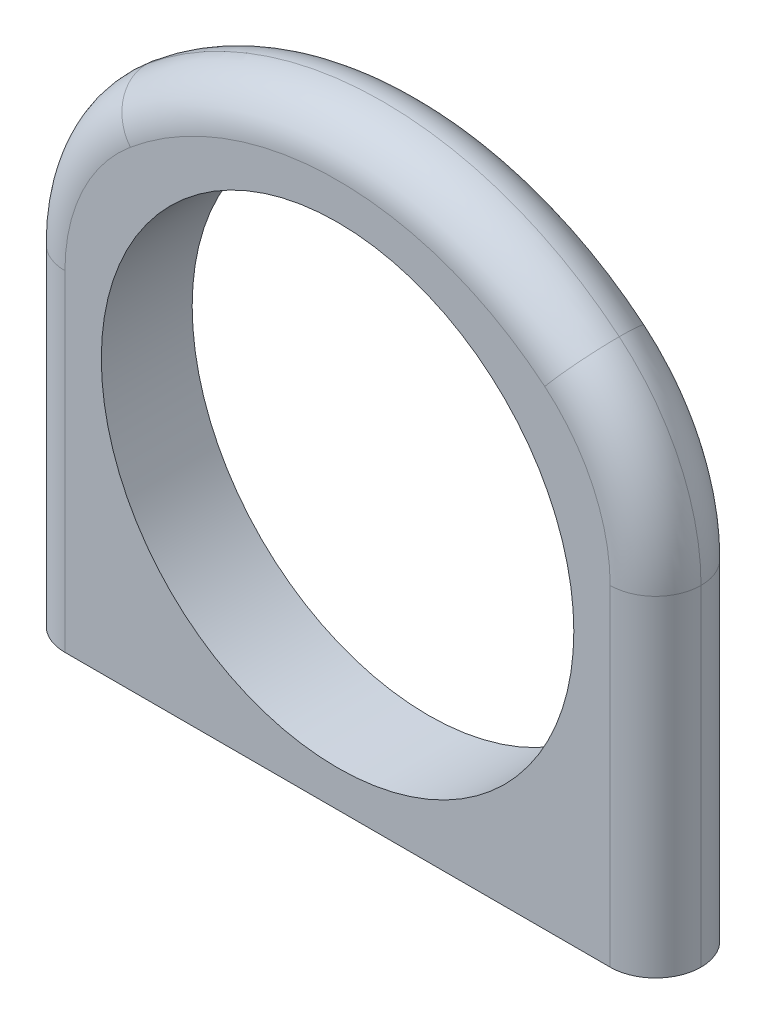
SolidWorks part; units mm, degrees
ref_plane "Front Plane" through (0, 0, 0) normal (0, 0, 1) x (1, 0, 0)
ref_plane "Top Plane" through (0, 0, 0) normal (0, 1, 0) x (1, 0, 0)
ref_plane "Right Plane" through (0, 0, 0) normal (1, 0, 0) x (0, 0, -1)
sketch "Sketch2" plane through (0, 0, 0) normal (0, 0, 1) x (1, 0, 0)
  line L0 (-35, 15) -> (35, 15)
  line L1 (-35, 35) -> (35, 35)
  line L2 (-35, 35) -> (-35, -30)
  line L3 (-35, -30) -> (35, -30)
  line L4 (35, 35) -> (35, -30)
  circle A0 centre (0, 0) radius 26
  arc A1 (-35, 15) -> (35, 15) centre (0, -5.625) cw
  point P10 (0, 0)
  dimension "D1" = 52
  dimension "D2" = 70
  dimension "D3" = 65
  dimension "D4" = 20
  dimension "D5" = 35
  dimension "D6" = 35
extrude "Boss-Extrude1" add sketch "Sketch2" along normal mid plane 10
sketch "Sketch3" plane through (0, -30, 0) normal (0, -1, 0) x (1, 0, 0)
  line L0 (55, 0) -> (-55, 0) construction
  line L1 (40, -25) -> (-40, -25)
  line L2 (40, -25) -> (40, 25)
  line L3 (40, 25) -> (-40, 25)
  line L4 (-40, -25) -> (-40, 25)
  line L5 (40, -25) -> (-40, 25) construction
  line L6 (40, 25) -> (-40, -25) construction
  circle A0 centre (-30, 15) radius 2
  circle A2 centre (30, 15) radius 2
  circle A3 centre (30, -15) radius 2
  circle A4 centre (-30, -15) radius 2
  point P0 (0, 0)
  dimension "D5" = 4
  dimension "D9" = 4
  dimension "D1" = 50
  dimension "D2" = 80
  dimension "D3" = 10
  dimension "D4" = 10
  dimension "D6" = 30
  dimension "D7" = 60
  dimension "D10" = 10
  dimension "D11" = 10
extrude "Boss-Extrude2" [suppressed] add sketch "Sketch3" against normal blind 5
hole_wizard "Tap Drill for M4x0.7 Tap1" [suppressed] positions "3DSketch5" profile "Sketch7" hole size "M4x0.7" standard "ANSI Metric"
sketch3d "3DSketch5"
  point P0 (-30, -35, 15)
  point P3 (-30, -35, -15)
  point P6 (30, -35, 15)
  point P9 (30, -35, -15)
sketch "Sketch7" plane through (-30, -35, 15) normal (1, 0, 0) x (0, 0, -1)
  line L0 (0, 0) -> (0, 70)
  line L1 (0, 70) -> (1.65, 70)
  line L2 (1.65, 70) -> (1.65, 0)
  line L5 (1.65, 0) -> (0, 0)
  line L11 (0, -6.35) -> (0, 107.95) construction
  dimension "Thru Hole Dia." = 3.3
  dimension "Thru Hole Depth" = 70
fillet "Fillet3" radius 25 2 edges at (35, 15, 0) (-35, 15, 0)
fillet "Fillet4" [suppressed] radius 5
sketch "Sketch8" [suppressed] plane through (0, -30, 0) normal (0, 1, 0) x (1, 0, 0)
  line L0 (40, -25) -> (-40, -25) construction
  line L1 (-11, -15) -> (11, -15)
  line L2 (-11, -15) -> (-11, -25)
  line L3 (-11, -25) -> (11, -25)
  line L4 (11, -15) -> (11, -25)
  point P6 (0, -25)
  dimension "D1" = 22
  dimension "D2" = 10
extrude "Cut-Extrude1" [suppressed] cut sketch "Sketch8" against normal up to surface (5 mm away)
sketch "Sketch9" plane through (0, -30, 0) normal (0, -1, 0) x (1, 0, 0)
  line L0 (-7.5, 0) -> (7.5, 0) construction
  circle A0 centre (-7.5, 0) radius 2
  circle A1 centre (7.5, 0) radius 2
  point P4 (0, 0)
  dimension "D2" = 4
  dimension "D3" = 4
  dimension "D1" = 15
extrude "Cut-Extrude2" cut sketch "Sketch9" against normal blind 4
fillet "Fillet5" radius 5 10 edges at (-35, -11.8096, 5) (-35, -11.8096, -5) (-32.6385, 16.9875, 5) (-32.6385, 16.9875, -5) (35, -11.8096, -5) (35, -11.8096, 5) (32.6385, 16.9875, 5) (32.6385, 16.9875, -5) (0, 35, 5) (0, 35, -5)
